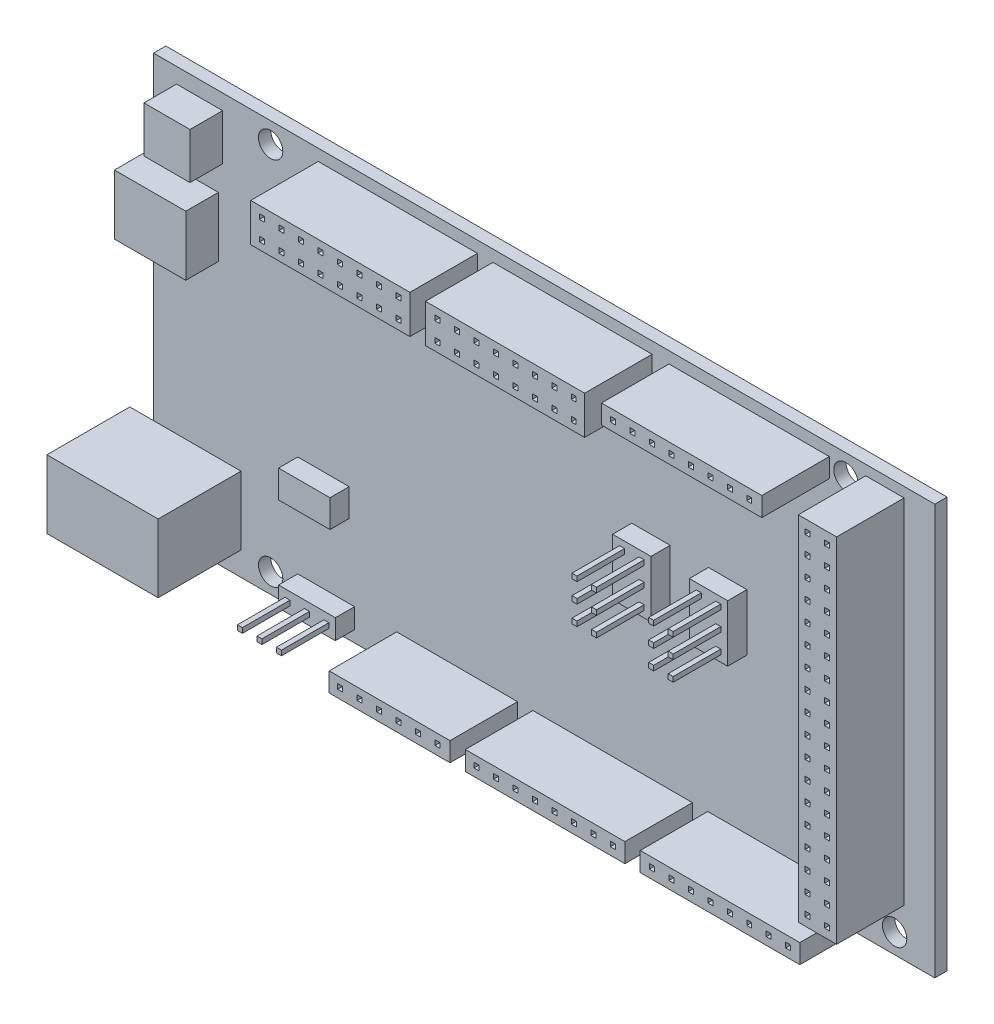
SolidWorks part; units mm, degrees
ref_plane "Front" through (0, 0, 0) normal (0, 0, 1) x (1, 0, 0)
ref_plane "Top" through (0, 0, 0) normal (0, 1, 0) x (1, 0, 0)
ref_plane "Right" through (0, 0, 0) normal (1, 0, 0) x (0, 0, -1)
sketch "sketchmap" plane through (0, 0, 0) normal (0, 0, 1) x (1, 0, 0)
  line L0 (-50.925, 26.75) -> (50.925, -26.75) construction
  line L1 (-50.925, 26.75) -> (50.925, 26.75)
  line L2 (-50.925, 26.75) -> (-50.925, -26.75)
  line L3 (-50.925, -26.75) -> (50.925, -26.75)
  line L4 (50.925, 26.75) -> (50.925, -26.75)
  dimension "D1" = 53.5
  dimension "D2" = 101.85
sketch "Sketch2" plane through (0, 0, 0) normal (0, 0, 1) x (1, 0, 0)
  line L0 (-35.6625, -24.1875) -> (45.6875, -24.1875) construction
  line L1 (-50.925, 26.75) -> (50.925, 26.75)
  line L2 (-50.925, 26.75) -> (-50.925, -26.75)
  line L3 (-50.925, -26.75) -> (50.925, -26.75)
  line L4 (50.925, 26.75) -> (50.925, -26.75)
  line L5 (-35.6625, 24.0625) -> (-35.6625, -24.1875) construction
  line L6 (39.3375, 24.0625) -> (-35.6625, 24.0625) construction
  line L10 (40.925, 24.0625) -> (50.925, 24.0625) construction
  line L11 (39.3375, 25.65) -> (39.3375, 26.75) construction
  circle A0 centre (45.6875, -24.1875) radius 1.5875
  circle A1 centre (-35.6625, -24.1875) radius 1.5875
  circle A2 centre (39.3375, 24.0625) radius 1.5875
  circle A3 centre (-35.6625, 24.0625) radius 1.5875
  dimension "D1" = 3.175
  dimension "D3" = 48.25
  dimension "D5" = 2.6875
  dimension "D4" = 5.2375
  dimension "D2" = 6.35
  dimension "D7" = 10
  dimension "D9" = 75
extrude "base board" add sketch "Sketch2" against normal blind 1.6
sketch "Sketch3" plane through (0, 0, 0) normal (0, 0, 1) x (1, 0, 0)
  line L1 (-29.457, 20.25) -> (-8.707, 20.25)
  line L2 (-29.457, 20.25) -> (-29.457, 25.25)
  line L3 (-29.457, 25.25) -> (-8.707, 25.25)
  line L4 (14.075, 20.25) -> (14.075, 25.25)
  line L5 (-50.925, 26.75) -> (50.925, 26.75) construction
  line L6 (50.925, 26.75) -> (50.925, -26.75) construction
  line L7 (16.275, 22.75) -> (37.175, 22.75)
  line L8 (16.275, 22.75) -> (16.275, 25.25)
  line L9 (16.275, 25.25) -> (37.175, 25.25)
  line L10 (37.175, 22.75) -> (37.175, 25.25)
  line L11 (41.925, 25.45) -> (46.925, 25.45)
  line L12 (41.925, 25.45) -> (41.925, -20.55)
  line L13 (41.925, -20.55) -> (46.925, -20.55)
  line L14 (46.925, 25.45) -> (46.925, -20.55)
  line L15 (-50.925, -26.75) -> (50.925, -26.75) construction
  line L16 (-8.707, 25.25) -> (-8.707, 20.25)
  line L17 (-6.675, 25.25) -> (-6.675, 20.25)
  line L18 (-6.675, 25.25) -> (14.075, 25.25)
  line L19 (-6.675, 20.25) -> (14.075, 20.25)
  line L20 (21.325, -25.25) -> (19.325, -25.25) construction
  line L21 (-19.225, -22.75) -> (-3.475, -22.75)
  line L22 (-19.225, -22.75) -> (-19.225, -25.25)
  line L23 (-19.225, -25.25) -> (-3.475, -25.25)
  line L24 (-3.475, -22.75) -> (-3.475, -25.25)
  line L25 (-1.475, -22.75) -> (19.325, -22.75)
  line L26 (-1.475, -22.75) -> (-1.475, -25.25)
  line L27 (-1.475, -25.25) -> (19.325, -25.25)
  line L28 (19.325, -22.75) -> (19.325, -25.25)
  line L29 (21.325, -22.75) -> (42.125, -22.75)
  line L30 (21.325, -22.75) -> (21.325, -25.25)
  line L31 (21.325, -25.25) -> (42.125, -25.25)
  line L32 (42.125, -22.75) -> (42.125, -25.25)
  line L33 (-3.475, -25.25) -> (-1.475, -25.25) construction
  line L34 (-1.475, -25.25) -> (-1.5179, -25.2056) construction
  line L35 (-50.925, 26.75) -> (-50.925, -26.75) construction
  line L36 (50.925, -26.75) -> (50.925, 26.75) construction
  dimension "D1" = 5
  dimension "D2" = 2.032
  dimension "D3" = 57.6
  dimension "D4" = 1.5
  dimension "D5" = 2.5
  dimension "D6" = 20.9
  dimension "D7" = 2.2
  dimension "D8" = 4
  dimension "D9" = 1.3
  dimension "D10" = 6.2
  dimension "D11" = 46
  dimension "D12" = 20.75
  dimension "D13" = 1.5
  dimension "D14" = 8.8
  dimension "D15" = 20.8
  dimension "D16" = 15.75
  dimension "D17" = 2
  dimension "D18" = 42.218
extrude "headers" add sketch "Sketch3" along normal blind 8.8
sketch "Sketch4" plane through (0, 0, 0) normal (0, 0, 1) x (1, 0, 0)
  line L0 (50.925, 26.75) -> (50.925, -26.75) construction
  line L1 (11.425, 4.85) -> (16.425, 4.85)
  line L2 (11.425, 4.85) -> (11.425, -2.55)
  line L3 (11.425, -2.55) -> (16.425, -2.55)
  line L4 (16.425, 4.85) -> (16.425, -2.55)
  line L5 (21.425, 4.85) -> (26.425, 4.85)
  line L6 (21.425, 4.85) -> (21.425, -2.55)
  line L7 (21.425, -2.55) -> (26.425, -2.55)
  line L8 (26.425, 4.85) -> (26.425, -2.55)
  line L9 (-50.925, 26.75) -> (50.925, 26.75) construction
  line L10 (-19.225, -22.75) -> (-19.225, -25.25) construction
  line L11 (-32.125, -22.65) -> (-24.725, -22.65)
  line L12 (-32.125, -22.65) -> (-32.125, -25.25)
  line L13 (-32.125, -25.25) -> (-24.725, -25.25)
  line L14 (-24.725, -22.65) -> (-24.725, -25.25)
  line L16 (-19.225, -25.25) -> (-3.475, -25.25) construction
  line L18 (-32.125, -9.45) -> (-25.425, -9.45)
  line L19 (-32.125, -9.45) -> (-32.125, -13.05)
  line L20 (-32.125, -13.05) -> (-25.425, -13.05)
  line L21 (-25.425, -9.45) -> (-25.425, -13.05)
  dimension "D1" = 5
  dimension "D2" = 7.4
  dimension "D3" = 29.5
  dimension "D4" = 5
  dimension "D5" = 29.3
  dimension "D6" = 2.6
  dimension "D7" = 7.4
  dimension "D8" = 5.5
  dimension "D9" = 6.7
  dimension "D10" = 3.6
  dimension "D11" = 9.6
extrude "pinbase" add sketch "Sketch4" along normal blind 2.5
sketch "Sketch5" plane through (0, 0, 0) normal (0, 0, 1) x (1, 0, 0)
  line L0 (-28.425, -22.65) -> (-28.425, -24.275) construction
  line L1 (-31.29, -23.625) -> (-30.64, -23.625)
  line L2 (-31.29, -23.625) -> (-31.29, -24.275)
  line L3 (-31.29, -24.275) -> (-30.64, -24.275)
  line L4 (-30.64, -23.625) -> (-30.64, -24.275)
  line L5 (-24.725, -22.65) -> (-32.125, -22.65) construction
  line L6 (-26.21, -23.625) -> (-26.21, -24.275)
  line L7 (-25.56, -24.275) -> (-26.21, -24.275)
  line L8 (-25.56, -23.625) -> (-25.56, -24.275)
  line L9 (-25.56, -23.625) -> (-26.21, -23.625)
  line L10 (-30.965, -24.275) -> (-30.965, -25.25) construction
  line L11 (-28.75, -24.275) -> (-28.1, -24.275)
  line L12 (-28.75, -24.275) -> (-28.75, -23.625)
  line L13 (-28.75, -23.625) -> (-28.1, -23.625)
  line L14 (-28.1, -24.275) -> (-28.1, -23.625)
  line L15 (-32.125, -25.25) -> (-24.725, -25.25) construction
  line L16 (-26.21, -23.625) -> (-25.56, -24.275) construction
  line L17 (-25.885, -22.65) -> (-25.885, -25.25) construction
  line L18 (-24.725, -22.65) -> (-32.125, -22.65) construction
  line L19 (13.925, 4.85) -> (13.925, -2.55) construction
  line L20 (12.33, 4.015) -> (12.98, 4.015)
  line L21 (12.33, 4.015) -> (12.33, 3.365)
  line L22 (12.33, 3.365) -> (12.98, 3.365)
  line L23 (12.98, 4.015) -> (12.98, 3.365)
  line L24 (16.425, 4.85) -> (11.425, 4.85) construction
  line L25 (11.425, -2.55) -> (16.425, -2.55) construction
  line L26 (15.52, 4.015) -> (15.52, 3.365)
  line L27 (15.52, 3.365) -> (14.87, 3.365)
  line L28 (14.87, 4.015) -> (14.87, 3.365)
  line L29 (15.52, 4.015) -> (14.87, 4.015)
  line L30 (12.33, 1.475) -> (12.98, 1.475)
  line L31 (12.33, 1.475) -> (12.33, 0.825)
  line L32 (12.33, 0.825) -> (12.98, 0.825)
  line L33 (12.98, 1.475) -> (12.98, 0.825)
  line L34 (15.52, 1.475) -> (15.52, 0.825)
  line L35 (15.52, 0.825) -> (14.87, 0.825)
  line L36 (14.87, 1.475) -> (14.87, 0.825)
  line L37 (15.52, 1.475) -> (14.87, 1.475)
  line L38 (12.33, -1.065) -> (12.98, -1.065)
  line L39 (12.33, -1.065) -> (12.33, -1.715)
  line L40 (12.33, -1.715) -> (12.98, -1.715)
  line L41 (12.98, -1.065) -> (12.98, -1.715)
  line L42 (15.52, -1.065) -> (15.52, -1.715)
  line L43 (15.52, -1.715) -> (14.87, -1.715)
  line L44 (14.87, -1.065) -> (14.87, -1.715)
  line L45 (15.52, -1.065) -> (14.87, -1.065)
  line L46 (13.925, 1.15) -> (12.98, 1.15) construction
  line L47 (16.425, 4.85) -> (21.425, 4.85) construction
  line L48 (18.925, 4.85) -> (18.925, 0) construction
  line L49 (22.33, -1.065) -> (22.98, -1.065)
  line L50 (22.98, -1.065) -> (22.98, -1.715)
  line L51 (22.33, -1.715) -> (22.98, -1.715)
  line L52 (22.33, -1.065) -> (22.33, -1.715)
  line L53 (22.33, 1.475) -> (22.98, 1.475)
  line L54 (22.98, 1.475) -> (22.98, 0.825)
  line L55 (22.33, 0.825) -> (22.98, 0.825)
  line L56 (22.33, 1.475) -> (22.33, 0.825)
  line L57 (22.33, 4.015) -> (22.98, 4.015)
  line L58 (22.98, 4.015) -> (22.98, 3.365)
  line L59 (22.33, 3.365) -> (22.98, 3.365)
  line L60 (22.33, 4.015) -> (22.33, 3.365)
  line L61 (24.87, -1.065) -> (24.87, -1.715)
  line L62 (25.52, -1.715) -> (24.87, -1.715)
  line L63 (25.52, -1.065) -> (25.52, -1.715)
  line L64 (25.52, -1.065) -> (24.87, -1.065)
  line L65 (24.87, 1.475) -> (24.87, 0.825)
  line L66 (25.52, 0.825) -> (24.87, 0.825)
  line L67 (25.52, 1.475) -> (25.52, 0.825)
  line L68 (25.52, 1.475) -> (24.87, 1.475)
  line L69 (24.87, 4.015) -> (24.87, 3.365)
  line L70 (25.52, 3.365) -> (24.87, 3.365)
  line L71 (25.52, 4.015) -> (25.52, 3.365)
  line L72 (25.52, 4.015) -> (24.87, 4.015)
  point P24 (-25.885, -23.95)
  dimension "D1" = 2.54
  dimension "D2" = 0.65
  dimension "D3" = 2.54
  dimension "D5" = 2.54
  dimension "D4" = 3
extrude "pins" add sketch "Sketch5" along normal blind 8.7 and the other way blind 3.2
sketch "Sketch6" plane through (0, 0, 0) normal (0, 0, 1) x (1, 0, 0)
  line L0 (-47.925, 18.75) -> (-41.925, 24.75) construction
  line L1 (-41.925, 24.75) -> (-47.925, 24.75)
  line L2 (-41.925, 24.75) -> (-41.925, 18.75)
  line L3 (-41.925, 18.75) -> (-47.925, 18.75)
  line L4 (-47.925, 24.75) -> (-47.925, 18.75)
  line L5 (-44.925, 21.75) -> (-47.925, 21.75) construction
  line L6 (-50.925, 26.75) -> (50.925, 26.75) construction
  line L7 (-47.925, 26.75) -> (-47.925, 24.75) construction
  line L8 (-50.925, 24.75) -> (-47.925, 24.75) construction
  line L9 (-50.925, 26.75) -> (-50.925, -26.75) construction
  line L11 (-42.475, 15.25) -> (-51.775, 15.25)
  line L12 (-42.475, 15.25) -> (-42.475, 7.45)
  line L13 (-42.475, 7.45) -> (-51.775, 7.45)
  line L14 (-51.775, 15.25) -> (-51.775, 7.45)
  dimension "D1" = 6
  dimension "D2" = 2
  dimension "D3" = 7.8
  dimension "D4" = 9.3
  dimension "D5" = 3
  dimension "D6" = 3.5
  dimension "D7" = 0.85
extrude "usbmini & button" add sketch "Sketch6" along normal blind 4.25
sketch "Sketch8" plane through (0, 0, 0) normal (0, 0, 1) x (1, 0, 0)
  line L0 (-50.925, 26.75) -> (-50.925, -26.75) construction
  line L1 (-39.525, -23.65) -> (-54.025, -23.65)
  line L2 (-39.525, -23.65) -> (-39.525, -14.75)
  line L3 (-39.525, -14.75) -> (-54.025, -14.75)
  line L4 (-54.025, -23.65) -> (-54.025, -14.75)
  line L5 (-50.925, -26.75) -> (50.925, -26.75) construction
  dimension "D1" = 8.9
  dimension "D2" = 14.5
  dimension "D3" = 3.1
  dimension "D4" = 3.1
extrude "power" add sketch "Sketch8" along normal blind 10.8
sketch "Sketch9" plane through (0, 0, -1.6) normal (0, 0, -1) x (-1, 0, 0)
  line L0 (50.925, 26.75) -> (50.925, -26.75) construction
  line L1 (42.175, -23.65) -> (45.175, -23.65)
  line L2 (42.175, -23.65) -> (42.175, -24.55)
  line L3 (42.175, -24.55) -> (45.175, -24.55)
  line L4 (45.175, -23.65) -> (45.175, -24.55)
  line L5 (50.925, -26.75) -> (-50.925, -26.75) construction
  line L6 (43.675, -23.65) -> (43.675, -17.3577) construction
  line L7 (39.975, -17.65) -> (40.875, -17.65)
  line L8 (39.975, -17.65) -> (39.975, -20.65)
  line L9 (39.975, -20.65) -> (40.875, -20.65)
  line L10 (40.875, -17.65) -> (40.875, -20.65)
  line L11 (46.475, -17.65) -> (46.475, -20.65)
  line L12 (47.375, -20.65) -> (46.475, -20.65)
  line L13 (47.375, -17.65) -> (47.375, -20.65)
  line L14 (47.375, -17.65) -> (46.475, -17.65)
  dimension "D1" = 3
  dimension "D2" = 0.9
  dimension "D3" = 5.75
  dimension "D4" = 2.2
  dimension "D5" = 5.6
  dimension "D6" = 3
extrude "underside solder tails" add sketch "Sketch9" along normal blind 1.8
sketch "Sketch10" plane through (0, 0, -1.6) normal (0, 0, -1) x (-1, 0, 0)
  line L0 (-41.925, 24) -> (-37.175, 24) construction
  line L2 (-37.175, 22.75) -> (-37.175, 25.25) construction
  line L3 (-41.925, 25.45) -> (-41.925, -20.55) construction
  line L4 (-41.925, 24) -> (-46.925, 24) construction
  line L5 (-46.925, -20.55) -> (-46.925, 25.45) construction
  line L6 (-44.425, 24) -> (-44.425, 25.45) construction
  line L7 (-46.925, 25.45) -> (-41.925, 25.45) construction
  line L8 (-46.02, 24.325) -> (-45.37, 23.675) construction
  line L9 (-46.02, 24.325) -> (-45.37, 24.325)
  line L10 (-46.02, 24.325) -> (-46.02, 23.675)
  line L11 (-46.02, 23.675) -> (-45.37, 23.675)
  line L12 (-45.37, 24.325) -> (-45.37, 23.675)
  line L13 (-45.695, 24) -> (-45.695, 24.325) construction
  line L14 (-24.87, 4.015) -> (-25.52, 4.015) construction
  point P17 (-45.695, 24)
  dimension "D1" = 2.54
extrude "underside rail tails" add sketch "Sketch10" along normal blind 1.6
pattern_linear "LPattern1" count 2 spacing 2.54 along (-1, 0, 0) count 18 spacing 2.54 along (0, -1, 0) of "underside rail tails"
sketch "Sketch11" plane through (0, 0, -1.6) normal (0, 0, -1) x (-1, 0, 0)
  line L0 (-45.37, 24.325) -> (-46.02, 24.325) construction
  line L1 (-35.86, 24.325) -> (-35.21, 24.325)
  line L2 (-35.86, 24.325) -> (-35.86, 23.675)
  line L3 (-35.86, 23.675) -> (-35.21, 23.675)
  line L4 (-35.21, 24.325) -> (-35.21, 23.675)
  line L5 (-42.83, 23.675) -> (-42.83, 24.325) construction
  line L6 (26.21, -24.275) -> (25.56, -24.275) construction
  line L7 (-40.94, -23.625) -> (-40.29, -23.625)
  line L8 (-40.94, -23.625) -> (-40.94, -24.275)
  line L9 (-40.94, -24.275) -> (-40.29, -24.275)
  line L10 (-40.29, -23.625) -> (-40.29, -24.275)
  line L11 (-42.83, -19.505) -> (-42.83, -18.855) construction
  dimension "D1" = 7.62
  dimension "D2" = 2.54
extrude "Boss-Extrude9" add sketch "Sketch11" along normal up to surface (1.6 mm away) up to face at (45.695, 24, -3.2)
pattern_linear "LPattern2" count 8 spacing 2.54 along (-1, 0, 0) of "Boss-Extrude9"
sketch "Sketch12" plane through (0, 0, -1.6) normal (0, 0, -1) x (-1, 0, 0)
  line L0 (-18.08, -23.625) -> (-17.43, -24.275) construction
  line L1 (-18.08, -23.625) -> (-17.43, -23.625)
  line L2 (-18.08, -23.625) -> (-18.08, -24.275)
  line L3 (-18.08, -24.275) -> (-17.43, -24.275)
  line L4 (-17.43, -23.625) -> (-17.43, -24.275)
  line L5 (-22.51, -23.625) -> (-23.16, -23.625) construction
  line L6 (-18.08, 24.325) -> (-18.08, 23.675) construction
extrude "Boss-Extrude10" add sketch "Sketch12" along normal up to surface (1.6 mm away) up to face at (22.835, -23.95, -3.2)
pattern_linear "LPattern3" count 15 spacing 2.54 along (-1, 0, 0) skipping (8, 0) of "Boss-Extrude10"
sketch "Sketch13" plane through (0, 0, -1.6) normal (0, 0, -1) x (-1, 0, 0)
  line L0 (-17.43, 24.325) -> (-18.08, 24.325) construction
  line L1 (-12.98, 24.325) -> (-12.33, 24.325)
  line L2 (-12.98, 24.325) -> (-12.98, 23.675)
  line L3 (-12.98, 23.675) -> (-12.33, 23.675)
  line L4 (-12.33, 24.325) -> (-12.33, 23.675)
  line L5 (-12.98, 3.365) -> (-12.98, 4.015) construction
extrude "Boss-Extrude11" add sketch "Sketch13" along normal up to surface (1.6 mm away) up to face at (45.695, 24, -3.2)
pattern_linear "LPattern4" count 17 spacing 2.54 along (-1, 0, 0) count 2 spacing 2.54 along (0, -1, 0) skipping (8, 0), (8, 1) of "Boss-Extrude11"
sketch "Sketch14" plane through (0, 0, 10.8) normal (0, 0, 1) x (1, 0, 0)
  line L0 (-20, 18.5) -> (40, -21.5) construction
  line L1 (-20, 18.5) -> (40, 18.5)
  line L2 (-20, 18.5) -> (-20, -21.5)
  line L3 (-20, -21.5) -> (40, -21.5)
  line L4 (40, 18.5) -> (40, -21.5)
  line L5 (10, -1.5) -> (40, -1.5) construction
  line L6 (10, -1.5) -> (10, 18.5) construction
  line L7 (10, -1.5) -> (-15, -1.5) construction
  line L8 (-16.75, -18.5) -> (36.75, 15.5) construction
  line L9 (-16.75, 15.5) -> (36.75, 15.5) construction
  line L10 (-16.75, 15.5) -> (-16.75, -18.5) construction
  line L11 (-16.75, -18.5) -> (36.75, -18.5) construction
  line L12 (36.75, 15.5) -> (36.75, -18.5) construction
  circle A0 centre (-16.75, 15.5) radius 1.65
  circle A1 centre (-16.75, -18.5) radius 1.65
  circle A2 centre (36.75, -18.5) radius 1.65
  circle A3 centre (36.75, 15.5) radius 1.65
  dimension "D8" = 3.3
  dimension "D1" = 60
  dimension "D2" = 40
  dimension "D3" = 25
  dimension "D4" = 1.5
  dimension "D5" = 10
  dimension "D6" = 34
  dimension "D7" = 53.5
sketch "Sketch15" plane through (0, 0, 8.8) normal (0, 0, 1) x (1, 0, 0)
  line L0 (46.02, 24.325) -> (46.02, 23.675) construction
  line L1 (46.02, 23.675) -> (45.37, 23.675) construction
  line L2 (45.37, 23.675) -> (45.37, 24.325) construction
  line L3 (45.37, 24.325) -> (46.02, 24.325) construction
  line L4 (46.02, 21.785) -> (46.02, 21.135) construction
  line L5 (46.02, 21.135) -> (45.37, 21.135) construction
  line L6 (45.37, 21.135) -> (45.37, 21.785) construction
  line L7 (45.37, 21.785) -> (46.02, 21.785) construction
  line L8 (46.02, 19.245) -> (46.02, 18.595) construction
  line L9 (46.02, 18.595) -> (45.37, 18.595) construction
  line L10 (45.37, 18.595) -> (45.37, 19.245) construction
  line L11 (45.37, 19.245) -> (46.02, 19.245) construction
  line L12 (46.02, 16.705) -> (46.02, 16.055) construction
  line L13 (46.02, 16.055) -> (45.37, 16.055) construction
  line L14 (45.37, 16.055) -> (45.37, 16.705) construction
  line L15 (45.37, 16.705) -> (46.02, 16.705) construction
  line L16 (46.02, 14.165) -> (46.02, 13.515) construction
  line L17 (46.02, 13.515) -> (45.37, 13.515) construction
  line L18 (45.37, 13.515) -> (45.37, 14.165) construction
  line L19 (45.37, 14.165) -> (46.02, 14.165) construction
  line L20 (46.02, 11.625) -> (46.02, 10.975) construction
  line L21 (46.02, 10.975) -> (45.37, 10.975) construction
  line L22 (45.37, 10.975) -> (45.37, 11.625) construction
  line L23 (45.37, 11.625) -> (46.02, 11.625) construction
  line L24 (46.02, 9.085) -> (46.02, 8.435) construction
  line L25 (46.02, 8.435) -> (45.37, 8.435) construction
  line L26 (45.37, 8.435) -> (45.37, 9.085) construction
  line L27 (45.37, 9.085) -> (46.02, 9.085) construction
  line L28 (46.02, 6.545) -> (46.02, 5.895) construction
  line L29 (46.02, 5.895) -> (45.37, 5.895) construction
  line L30 (45.37, 5.895) -> (45.37, 6.545) construction
  line L31 (45.37, 6.545) -> (46.02, 6.545) construction
  line L32 (46.02, 4.005) -> (46.02, 3.355) construction
  line L33 (46.02, 3.355) -> (45.37, 3.355) construction
  line L34 (45.37, 3.355) -> (45.37, 4.005) construction
  line L35 (45.37, 4.005) -> (46.02, 4.005) construction
  line L36 (46.02, 1.465) -> (46.02, 0.815) construction
  line L37 (46.02, 0.815) -> (45.37, 0.815) construction
  line L38 (45.37, 0.815) -> (45.37, 1.465) construction
  line L39 (45.37, 1.465) -> (46.02, 1.465) construction
  line L40 (46.02, -1.075) -> (46.02, -1.725) construction
  line L41 (46.02, -1.725) -> (45.37, -1.725) construction
  line L42 (45.37, -1.725) -> (45.37, -1.075) construction
  line L43 (45.37, -1.075) -> (46.02, -1.075) construction
  line L44 (46.02, -3.615) -> (46.02, -4.265) construction
  line L45 (46.02, -4.265) -> (45.37, -4.265) construction
  line L46 (45.37, -4.265) -> (45.37, -3.615) construction
  line L47 (45.37, -3.615) -> (46.02, -3.615) construction
  line L48 (46.02, -6.155) -> (46.02, -6.805) construction
  line L49 (46.02, -6.805) -> (45.37, -6.805) construction
  line L50 (45.37, -6.805) -> (45.37, -6.155) construction
  line L51 (45.37, -6.155) -> (46.02, -6.155) construction
  line L52 (46.02, -8.695) -> (46.02, -9.345) construction
  line L53 (46.02, -9.345) -> (45.37, -9.345) construction
  line L54 (45.37, -9.345) -> (45.37, -8.695) construction
  line L55 (45.37, -8.695) -> (46.02, -8.695) construction
  line L56 (46.02, -11.235) -> (46.02, -11.885) construction
  line L57 (46.02, -11.885) -> (45.37, -11.885) construction
  line L58 (45.37, -11.885) -> (45.37, -11.235) construction
  line L59 (45.37, -11.235) -> (46.02, -11.235) construction
  line L60 (46.02, -13.775) -> (46.02, -14.425) construction
  line L61 (46.02, -14.425) -> (45.37, -14.425) construction
  line L62 (45.37, -14.425) -> (45.37, -13.775) construction
  line L63 (45.37, -13.775) -> (46.02, -13.775) construction
  line L64 (46.02, -16.315) -> (46.02, -16.965) construction
  line L65 (46.02, -16.965) -> (45.37, -16.965) construction
  line L66 (45.37, -16.965) -> (45.37, -16.315) construction
  line L67 (45.37, -16.315) -> (46.02, -16.315) construction
  line L68 (46.02, -18.855) -> (46.02, -19.505) construction
  line L69 (46.02, -19.505) -> (45.37, -19.505) construction
  line L70 (45.37, -19.505) -> (45.37, -18.855) construction
  line L71 (45.37, -18.855) -> (46.02, -18.855) construction
  line L72 (46.02, 24.325) -> (46.02, 23.675)
  line L73 (46.02, 23.675) -> (45.37, 23.675)
  line L74 (45.37, 23.675) -> (45.37, 24.325)
  line L75 (45.37, 24.325) -> (46.02, 24.325)
  line L76 (46.02, 21.785) -> (46.02, 21.135)
  line L77 (46.02, 21.135) -> (45.37, 21.135)
  line L78 (45.37, 21.135) -> (45.37, 21.785)
  line L79 (45.37, 21.785) -> (46.02, 21.785)
  line L80 (46.02, 19.245) -> (46.02, 18.595)
  line L81 (46.02, 18.595) -> (45.37, 18.595)
  line L82 (45.37, 18.595) -> (45.37, 19.245)
  line L83 (45.37, 19.245) -> (46.02, 19.245)
  line L84 (46.02, 16.705) -> (46.02, 16.055)
  line L85 (46.02, 16.055) -> (45.37, 16.055)
  line L86 (45.37, 16.055) -> (45.37, 16.705)
  line L87 (45.37, 16.705) -> (46.02, 16.705)
  line L88 (46.02, 14.165) -> (46.02, 13.515)
  line L89 (46.02, 13.515) -> (45.37, 13.515)
  line L90 (45.37, 13.515) -> (45.37, 14.165)
  line L91 (45.37, 14.165) -> (46.02, 14.165)
  line L92 (46.02, 11.625) -> (46.02, 10.975)
  line L93 (46.02, 10.975) -> (45.37, 10.975)
  line L94 (45.37, 10.975) -> (45.37, 11.625)
  line L95 (45.37, 11.625) -> (46.02, 11.625)
  line L96 (46.02, 9.085) -> (46.02, 8.435)
  line L97 (46.02, 8.435) -> (45.37, 8.435)
  line L98 (45.37, 8.435) -> (45.37, 9.085)
  line L99 (45.37, 9.085) -> (46.02, 9.085)
  line L100 (46.02, 6.545) -> (46.02, 5.895)
  line L101 (46.02, 5.895) -> (45.37, 5.895)
  line L102 (45.37, 5.895) -> (45.37, 6.545)
  line L103 (45.37, 6.545) -> (46.02, 6.545)
  line L104 (46.02, 4.005) -> (46.02, 3.355)
  line L105 (46.02, 3.355) -> (45.37, 3.355)
  line L106 (45.37, 3.355) -> (45.37, 4.005)
  line L107 (45.37, 4.005) -> (46.02, 4.005)
  line L108 (46.02, 1.465) -> (46.02, 0.815)
  line L109 (46.02, 0.815) -> (45.37, 0.815)
  line L110 (45.37, 0.815) -> (45.37, 1.465)
  line L111 (45.37, 1.465) -> (46.02, 1.465)
  line L112 (46.02, -1.075) -> (46.02, -1.725)
  line L113 (46.02, -1.725) -> (45.37, -1.725)
  line L114 (45.37, -1.725) -> (45.37, -1.075)
  line L115 (45.37, -1.075) -> (46.02, -1.075)
  line L116 (46.02, -3.615) -> (46.02, -4.265)
  line L117 (46.02, -4.265) -> (45.37, -4.265)
  line L118 (45.37, -4.265) -> (45.37, -3.615)
  line L119 (45.37, -3.615) -> (46.02, -3.615)
  line L120 (46.02, -6.155) -> (46.02, -6.805)
  line L121 (46.02, -6.805) -> (45.37, -6.805)
  line L122 (45.37, -6.805) -> (45.37, -6.155)
  line L123 (45.37, -6.155) -> (46.02, -6.155)
  line L124 (46.02, -8.695) -> (46.02, -9.345)
  line L125 (46.02, -9.345) -> (45.37, -9.345)
  line L126 (45.37, -9.345) -> (45.37, -8.695)
  line L127 (45.37, -8.695) -> (46.02, -8.695)
  line L128 (46.02, -11.235) -> (46.02, -11.885)
  line L129 (46.02, -11.885) -> (45.37, -11.885)
  line L130 (45.37, -11.885) -> (45.37, -11.235)
  line L131 (45.37, -11.235) -> (46.02, -11.235)
  line L132 (46.02, -13.775) -> (46.02, -14.425)
  line L133 (46.02, -14.425) -> (45.37, -14.425)
  line L134 (45.37, -14.425) -> (45.37, -13.775)
  line L135 (45.37, -13.775) -> (46.02, -13.775)
  line L136 (46.02, -16.315) -> (46.02, -16.965)
  line L137 (46.02, -16.965) -> (45.37, -16.965)
  line L138 (45.37, -16.965) -> (45.37, -16.315)
  line L139 (45.37, -16.315) -> (46.02, -16.315)
  line L140 (46.02, -18.855) -> (46.02, -19.505)
  line L141 (46.02, -19.505) -> (45.37, -19.505)
  line L142 (45.37, -19.505) -> (45.37, -18.855)
  line L143 (45.37, -18.855) -> (46.02, -18.855)
  line L144 (43.48, 24.325) -> (43.48, 23.675) construction
  line L145 (43.48, 23.675) -> (42.83, 23.675) construction
  line L146 (42.83, 23.675) -> (42.83, 24.325) construction
  line L147 (42.83, 24.325) -> (43.48, 24.325) construction
  line L148 (43.48, 21.785) -> (43.48, 21.135) construction
  line L149 (43.48, 21.135) -> (42.83, 21.135) construction
  line L150 (42.83, 21.135) -> (42.83, 21.785) construction
  line L151 (42.83, 21.785) -> (43.48, 21.785) construction
  line L152 (43.48, 19.245) -> (43.48, 18.595) construction
  line L153 (43.48, 18.595) -> (42.83, 18.595) construction
  line L154 (42.83, 18.595) -> (42.83, 19.245) construction
  line L155 (42.83, 19.245) -> (43.48, 19.245) construction
  line L156 (43.48, 16.705) -> (43.48, 16.055) construction
  line L157 (43.48, 16.055) -> (42.83, 16.055) construction
  line L158 (42.83, 16.055) -> (42.83, 16.705) construction
  line L159 (42.83, 16.705) -> (43.48, 16.705) construction
  line L160 (43.48, 14.165) -> (43.48, 13.515) construction
  line L161 (43.48, 13.515) -> (42.83, 13.515) construction
  line L162 (42.83, 13.515) -> (42.83, 14.165) construction
  line L163 (42.83, 14.165) -> (43.48, 14.165) construction
  line L164 (43.48, 11.625) -> (43.48, 10.975) construction
  line L165 (43.48, 10.975) -> (42.83, 10.975) construction
  line L166 (42.83, 10.975) -> (42.83, 11.625) construction
  line L167 (42.83, 11.625) -> (43.48, 11.625) construction
  line L168 (43.48, 9.085) -> (43.48, 8.435) construction
  line L169 (43.48, 8.435) -> (42.83, 8.435) construction
  line L170 (42.83, 8.435) -> (42.83, 9.085) construction
  line L171 (42.83, 9.085) -> (43.48, 9.085) construction
  line L172 (43.48, 6.545) -> (43.48, 5.895) construction
  line L173 (43.48, 5.895) -> (42.83, 5.895) construction
  line L174 (42.83, 5.895) -> (42.83, 6.545) construction
  line L175 (42.83, 6.545) -> (43.48, 6.545) construction
  line L176 (43.48, 4.005) -> (43.48, 3.355) construction
  line L177 (43.48, 3.355) -> (42.83, 3.355) construction
  line L178 (42.83, 3.355) -> (42.83, 4.005) construction
  line L179 (42.83, 4.005) -> (43.48, 4.005) construction
  line L180 (43.48, 1.465) -> (43.48, 0.815) construction
  line L181 (43.48, 0.815) -> (42.83, 0.815) construction
  line L182 (42.83, 0.815) -> (42.83, 1.465) construction
  line L183 (42.83, 1.465) -> (43.48, 1.465) construction
  line L184 (43.48, -1.075) -> (43.48, -1.725) construction
  line L185 (43.48, -1.725) -> (42.83, -1.725) construction
  line L186 (42.83, -1.725) -> (42.83, -1.075) construction
  line L187 (42.83, -1.075) -> (43.48, -1.075) construction
  line L188 (43.48, -3.615) -> (43.48, -4.265) construction
  line L189 (43.48, -4.265) -> (42.83, -4.265) construction
  line L190 (42.83, -4.265) -> (42.83, -3.615) construction
  line L191 (42.83, -3.615) -> (43.48, -3.615) construction
  line L192 (43.48, -6.155) -> (43.48, -6.805) construction
  line L193 (43.48, -6.805) -> (42.83, -6.805) construction
  line L194 (42.83, -6.805) -> (42.83, -6.155) construction
  line L195 (42.83, -6.155) -> (43.48, -6.155) construction
  line L196 (43.48, -8.695) -> (43.48, -9.345) construction
  line L197 (43.48, -9.345) -> (42.83, -9.345) construction
  line L198 (42.83, -9.345) -> (42.83, -8.695) construction
  line L199 (42.83, -8.695) -> (43.48, -8.695) construction
  line L200 (43.48, -11.235) -> (43.48, -11.885) construction
  line L201 (43.48, -11.885) -> (42.83, -11.885) construction
  line L202 (42.83, -11.885) -> (42.83, -11.235) construction
  line L203 (42.83, -11.235) -> (43.48, -11.235) construction
  line L204 (43.48, -13.775) -> (43.48, -14.425) construction
  line L205 (43.48, -14.425) -> (42.83, -14.425) construction
  line L206 (42.83, -14.425) -> (42.83, -13.775) construction
  line L207 (42.83, -13.775) -> (43.48, -13.775) construction
  line L208 (43.48, -16.315) -> (43.48, -16.965) construction
  line L209 (43.48, -16.965) -> (42.83, -16.965) construction
  line L210 (42.83, -16.965) -> (42.83, -16.315) construction
  line L211 (42.83, -16.315) -> (43.48, -16.315) construction
  line L212 (43.48, -18.855) -> (43.48, -19.505) construction
  line L213 (43.48, -19.505) -> (42.83, -19.505) construction
  line L214 (42.83, -19.505) -> (42.83, -18.855) construction
  line L215 (42.83, -18.855) -> (43.48, -18.855) construction
  line L216 (43.48, 24.325) -> (43.48, 23.675)
  line L217 (43.48, 23.675) -> (42.83, 23.675)
  line L218 (42.83, 23.675) -> (42.83, 24.325)
  line L219 (42.83, 24.325) -> (43.48, 24.325)
  line L220 (43.48, 21.785) -> (43.48, 21.135)
  line L221 (43.48, 21.135) -> (42.83, 21.135)
  line L222 (42.83, 21.135) -> (42.83, 21.785)
  line L223 (42.83, 21.785) -> (43.48, 21.785)
  line L224 (43.48, 19.245) -> (43.48, 18.595)
  line L225 (43.48, 18.595) -> (42.83, 18.595)
  line L226 (42.83, 18.595) -> (42.83, 19.245)
  line L227 (42.83, 19.245) -> (43.48, 19.245)
  line L228 (43.48, 16.705) -> (43.48, 16.055)
  line L229 (43.48, 16.055) -> (42.83, 16.055)
  line L230 (42.83, 16.055) -> (42.83, 16.705)
  line L231 (42.83, 16.705) -> (43.48, 16.705)
  line L232 (43.48, 14.165) -> (43.48, 13.515)
  line L233 (43.48, 13.515) -> (42.83, 13.515)
  line L234 (42.83, 13.515) -> (42.83, 14.165)
  line L235 (42.83, 14.165) -> (43.48, 14.165)
  line L236 (43.48, 11.625) -> (43.48, 10.975)
  line L237 (43.48, 10.975) -> (42.83, 10.975)
  line L238 (42.83, 10.975) -> (42.83, 11.625)
  line L239 (42.83, 11.625) -> (43.48, 11.625)
  line L240 (43.48, 9.085) -> (43.48, 8.435)
  line L241 (43.48, 8.435) -> (42.83, 8.435)
  line L242 (42.83, 8.435) -> (42.83, 9.085)
  line L243 (42.83, 9.085) -> (43.48, 9.085)
  line L244 (43.48, 6.545) -> (43.48, 5.895)
  line L245 (43.48, 5.895) -> (42.83, 5.895)
  line L246 (42.83, 5.895) -> (42.83, 6.545)
  line L247 (42.83, 6.545) -> (43.48, 6.545)
  line L248 (43.48, 4.005) -> (43.48, 3.355)
  line L249 (43.48, 3.355) -> (42.83, 3.355)
  line L250 (42.83, 3.355) -> (42.83, 4.005)
  line L251 (42.83, 4.005) -> (43.48, 4.005)
  line L252 (43.48, 1.465) -> (43.48, 0.815)
  line L253 (43.48, 0.815) -> (42.83, 0.815)
  line L254 (42.83, 0.815) -> (42.83, 1.465)
  line L255 (42.83, 1.465) -> (43.48, 1.465)
  line L256 (43.48, -1.075) -> (43.48, -1.725)
  line L257 (43.48, -1.725) -> (42.83, -1.725)
  line L258 (42.83, -1.725) -> (42.83, -1.075)
  line L259 (42.83, -1.075) -> (43.48, -1.075)
  line L260 (43.48, -3.615) -> (43.48, -4.265)
  line L261 (43.48, -4.265) -> (42.83, -4.265)
  line L262 (42.83, -4.265) -> (42.83, -3.615)
  line L263 (42.83, -3.615) -> (43.48, -3.615)
  line L264 (43.48, -6.155) -> (43.48, -6.805)
  line L265 (43.48, -6.805) -> (42.83, -6.805)
  line L266 (42.83, -6.805) -> (42.83, -6.155)
  line L267 (42.83, -6.155) -> (43.48, -6.155)
  line L268 (43.48, -8.695) -> (43.48, -9.345)
  line L269 (43.48, -9.345) -> (42.83, -9.345)
  line L270 (42.83, -9.345) -> (42.83, -8.695)
  line L271 (42.83, -8.695) -> (43.48, -8.695)
  line L272 (43.48, -11.235) -> (43.48, -11.885)
  line L273 (43.48, -11.885) -> (42.83, -11.885)
  line L274 (42.83, -11.885) -> (42.83, -11.235)
  line L275 (42.83, -11.235) -> (43.48, -11.235)
  line L276 (43.48, -13.775) -> (43.48, -14.425)
  line L277 (43.48, -14.425) -> (42.83, -14.425)
  line L278 (42.83, -14.425) -> (42.83, -13.775)
  line L279 (42.83, -13.775) -> (43.48, -13.775)
  line L280 (43.48, -16.315) -> (43.48, -16.965)
  line L281 (43.48, -16.965) -> (42.83, -16.965)
  line L282 (42.83, -16.965) -> (42.83, -16.315)
  line L283 (42.83, -16.315) -> (43.48, -16.315)
  line L284 (43.48, -18.855) -> (43.48, -19.505)
  line L285 (43.48, -19.505) -> (42.83, -19.505)
  line L286 (42.83, -19.505) -> (42.83, -18.855)
  line L287 (42.83, -18.855) -> (43.48, -18.855)
  line L288 (35.21, 24.325) -> (35.86, 24.325) construction
  line L289 (35.86, 24.325) -> (35.86, 23.675) construction
  line L290 (35.86, 23.675) -> (35.21, 23.675) construction
  line L291 (35.21, 23.675) -> (35.21, 24.325) construction
  line L292 (32.67, 24.325) -> (33.32, 24.325) construction
  line L293 (33.32, 24.325) -> (33.32, 23.675) construction
  line L294 (33.32, 23.675) -> (32.67, 23.675) construction
  line L295 (32.67, 23.675) -> (32.67, 24.325) construction
  line L296 (30.13, 24.325) -> (30.78, 24.325) construction
  line L297 (30.78, 24.325) -> (30.78, 23.675) construction
  line L298 (30.78, 23.675) -> (30.13, 23.675) construction
  line L299 (30.13, 23.675) -> (30.13, 24.325) construction
  line L300 (27.59, 24.325) -> (28.24, 24.325) construction
  line L301 (28.24, 24.325) -> (28.24, 23.675) construction
  line L302 (28.24, 23.675) -> (27.59, 23.675) construction
  line L303 (27.59, 23.675) -> (27.59, 24.325) construction
  line L304 (25.05, 24.325) -> (25.7, 24.325) construction
  line L305 (25.7, 24.325) -> (25.7, 23.675) construction
  line L306 (25.7, 23.675) -> (25.05, 23.675) construction
  line L307 (25.05, 23.675) -> (25.05, 24.325) construction
  line L308 (22.51, 24.325) -> (23.16, 24.325) construction
  line L309 (23.16, 24.325) -> (23.16, 23.675) construction
  line L310 (23.16, 23.675) -> (22.51, 23.675) construction
  line L311 (22.51, 23.675) -> (22.51, 24.325) construction
  line L312 (19.97, 24.325) -> (20.62, 24.325) construction
  line L313 (20.62, 24.325) -> (20.62, 23.675) construction
  line L314 (20.62, 23.675) -> (19.97, 23.675) construction
  line L315 (19.97, 23.675) -> (19.97, 24.325) construction
  line L316 (17.43, 24.325) -> (18.08, 24.325) construction
  line L317 (18.08, 24.325) -> (18.08, 23.675) construction
  line L318 (18.08, 23.675) -> (17.43, 23.675) construction
  line L319 (17.43, 23.675) -> (17.43, 24.325) construction
  line L320 (12.33, 24.325) -> (12.98, 24.325) construction
  line L321 (12.98, 24.325) -> (12.98, 23.675) construction
  line L322 (12.98, 23.675) -> (12.33, 23.675) construction
  line L323 (12.33, 23.675) -> (12.33, 24.325) construction
  line L324 (12.33, 21.785) -> (12.98, 21.785) construction
  line L325 (12.98, 21.785) -> (12.98, 21.135) construction
  line L326 (12.98, 21.135) -> (12.33, 21.135) construction
  line L327 (12.33, 21.135) -> (12.33, 21.785) construction
  line L328 (9.79, 24.325) -> (10.44, 24.325) construction
  line L329 (10.44, 24.325) -> (10.44, 23.675) construction
  line L330 (10.44, 23.675) -> (9.79, 23.675) construction
  line L331 (9.79, 23.675) -> (9.79, 24.325) construction
  line L332 (9.79, 21.785) -> (10.44, 21.785) construction
  line L333 (10.44, 21.785) -> (10.44, 21.135) construction
  line L334 (10.44, 21.135) -> (9.79, 21.135) construction
  line L335 (9.79, 21.135) -> (9.79, 21.785) construction
  line L336 (7.25, 24.325) -> (7.9, 24.325) construction
  line L337 (7.9, 24.325) -> (7.9, 23.675) construction
  line L338 (7.9, 23.675) -> (7.25, 23.675) construction
  line L339 (7.25, 23.675) -> (7.25, 24.325) construction
  line L340 (7.25, 21.785) -> (7.9, 21.785) construction
  line L341 (7.9, 21.785) -> (7.9, 21.135) construction
  line L342 (7.9, 21.135) -> (7.25, 21.135) construction
  line L343 (7.25, 21.135) -> (7.25, 21.785) construction
  line L344 (4.71, 24.325) -> (5.36, 24.325) construction
  line L345 (5.36, 24.325) -> (5.36, 23.675) construction
  line L346 (5.36, 23.675) -> (4.71, 23.675) construction
  line L347 (4.71, 23.675) -> (4.71, 24.325) construction
  line L348 (4.71, 21.785) -> (5.36, 21.785) construction
  line L349 (5.36, 21.785) -> (5.36, 21.135) construction
  line L350 (5.36, 21.135) -> (4.71, 21.135) construction
  line L351 (4.71, 21.135) -> (4.71, 21.785) construction
  line L352 (2.17, 24.325) -> (2.82, 24.325) construction
  line L353 (2.82, 24.325) -> (2.82, 23.675) construction
  line L354 (2.82, 23.675) -> (2.17, 23.675) construction
  line L355 (2.17, 23.675) -> (2.17, 24.325) construction
  line L356 (2.17, 21.785) -> (2.82, 21.785) construction
  line L357 (2.82, 21.785) -> (2.82, 21.135) construction
  line L358 (2.82, 21.135) -> (2.17, 21.135) construction
  line L359 (2.17, 21.135) -> (2.17, 21.785) construction
  line L360 (-0.37, 24.325) -> (0.28, 24.325) construction
  line L361 (0.28, 24.325) -> (0.28, 23.675) construction
  line L362 (0.28, 23.675) -> (-0.37, 23.675) construction
  line L363 (-0.37, 23.675) -> (-0.37, 24.325) construction
  line L364 (-0.37, 21.785) -> (0.28, 21.785) construction
  line L365 (0.28, 21.785) -> (0.28, 21.135) construction
  line L366 (0.28, 21.135) -> (-0.37, 21.135) construction
  line L367 (-0.37, 21.135) -> (-0.37, 21.785) construction
  line L368 (-2.91, 24.325) -> (-2.26, 24.325) construction
  line L369 (-2.26, 24.325) -> (-2.26, 23.675) construction
  line L370 (-2.26, 23.675) -> (-2.91, 23.675) construction
  line L371 (-2.91, 23.675) -> (-2.91, 24.325) construction
  line L372 (-2.91, 21.785) -> (-2.26, 21.785) construction
  line L373 (-2.26, 21.785) -> (-2.26, 21.135) construction
  line L374 (-2.26, 21.135) -> (-2.91, 21.135) construction
  line L375 (-2.91, 21.135) -> (-2.91, 21.785) construction
  line L376 (-5.45, 24.325) -> (-4.8, 24.325) construction
  line L377 (-4.8, 24.325) -> (-4.8, 23.675) construction
  line L378 (-4.8, 23.675) -> (-5.45, 23.675) construction
  line L379 (-5.45, 23.675) -> (-5.45, 24.325) construction
  line L380 (-5.45, 21.785) -> (-4.8, 21.785) construction
  line L381 (-4.8, 21.785) -> (-4.8, 21.135) construction
  line L382 (-4.8, 21.135) -> (-5.45, 21.135) construction
  line L383 (-5.45, 21.135) -> (-5.45, 21.785) construction
  line L384 (-10.53, 24.325) -> (-9.88, 24.325) construction
  line L385 (-9.88, 24.325) -> (-9.88, 23.675) construction
  line L386 (-9.88, 23.675) -> (-10.53, 23.675) construction
  line L387 (-10.53, 23.675) -> (-10.53, 24.325) construction
  line L388 (-10.53, 21.785) -> (-9.88, 21.785) construction
  line L389 (-9.88, 21.785) -> (-9.88, 21.135) construction
  line L390 (-9.88, 21.135) -> (-10.53, 21.135) construction
  line L391 (-10.53, 21.135) -> (-10.53, 21.785) construction
  line L392 (-13.07, 24.325) -> (-12.42, 24.325) construction
  line L393 (-12.42, 24.325) -> (-12.42, 23.675) construction
  line L394 (-12.42, 23.675) -> (-13.07, 23.675) construction
  line L395 (-13.07, 23.675) -> (-13.07, 24.325) construction
  line L396 (-13.07, 21.785) -> (-12.42, 21.785) construction
  line L397 (-12.42, 21.785) -> (-12.42, 21.135) construction
  line L398 (-12.42, 21.135) -> (-13.07, 21.135) construction
  line L399 (-13.07, 21.135) -> (-13.07, 21.785) construction
  line L400 (-15.61, 24.325) -> (-14.96, 24.325) construction
  line L401 (-14.96, 24.325) -> (-14.96, 23.675) construction
  line L402 (-14.96, 23.675) -> (-15.61, 23.675) construction
  line L403 (-15.61, 23.675) -> (-15.61, 24.325) construction
  line L404 (-15.61, 21.785) -> (-14.96, 21.785) construction
  line L405 (-14.96, 21.785) -> (-14.96, 21.135) construction
  line L406 (-14.96, 21.135) -> (-15.61, 21.135) construction
  line L407 (-15.61, 21.135) -> (-15.61, 21.785) construction
  line L408 (-18.15, 24.325) -> (-17.5, 24.325) construction
  line L409 (-17.5, 24.325) -> (-17.5, 23.675) construction
  line L410 (-17.5, 23.675) -> (-18.15, 23.675) construction
  line L411 (-18.15, 23.675) -> (-18.15, 24.325) construction
  line L412 (-18.15, 21.785) -> (-17.5, 21.785) construction
  line L413 (-17.5, 21.785) -> (-17.5, 21.135) construction
  line L414 (-17.5, 21.135) -> (-18.15, 21.135) construction
  line L415 (-18.15, 21.135) -> (-18.15, 21.785) construction
  line L416 (-20.69, 24.325) -> (-20.04, 24.325) construction
  line L417 (-20.04, 24.325) -> (-20.04, 23.675) construction
  line L418 (-20.04, 23.675) -> (-20.69, 23.675) construction
  line L419 (-20.69, 23.675) -> (-20.69, 24.325) construction
  line L420 (-20.69, 21.785) -> (-20.04, 21.785) construction
  line L421 (-20.04, 21.785) -> (-20.04, 21.135) construction
  line L422 (-20.04, 21.135) -> (-20.69, 21.135) construction
  line L423 (-20.69, 21.135) -> (-20.69, 21.785) construction
  line L424 (-23.23, 24.325) -> (-22.58, 24.325) construction
  line L425 (-22.58, 24.325) -> (-22.58, 23.675) construction
  line L426 (-22.58, 23.675) -> (-23.23, 23.675) construction
  line L427 (-23.23, 23.675) -> (-23.23, 24.325) construction
  line L428 (-23.23, 21.785) -> (-22.58, 21.785) construction
  line L429 (-22.58, 21.785) -> (-22.58, 21.135) construction
  line L430 (-22.58, 21.135) -> (-23.23, 21.135) construction
  line L431 (-23.23, 21.135) -> (-23.23, 21.785) construction
  line L432 (-25.77, 24.325) -> (-25.12, 24.325) construction
  line L433 (-25.12, 24.325) -> (-25.12, 23.675) construction
  line L434 (-25.12, 23.675) -> (-25.77, 23.675) construction
  line L435 (-25.77, 23.675) -> (-25.77, 24.325) construction
  line L436 (-25.77, 21.785) -> (-25.12, 21.785) construction
  line L437 (-25.12, 21.785) -> (-25.12, 21.135) construction
  line L438 (-25.12, 21.135) -> (-25.77, 21.135) construction
  line L439 (-25.77, 21.135) -> (-25.77, 21.785) construction
  line L440 (-28.31, 24.325) -> (-27.66, 24.325) construction
  line L441 (-27.66, 24.325) -> (-27.66, 23.675) construction
  line L442 (-27.66, 23.675) -> (-28.31, 23.675) construction
  line L443 (-28.31, 23.675) -> (-28.31, 24.325) construction
  line L444 (-28.31, 21.785) -> (-27.66, 21.785) construction
  line L445 (-27.66, 21.785) -> (-27.66, 21.135) construction
  line L446 (-27.66, 21.135) -> (-28.31, 21.135) construction
  line L447 (-28.31, 21.135) -> (-28.31, 21.785) construction
  line L448 (35.21, 24.325) -> (35.86, 24.325)
  line L449 (35.86, 24.325) -> (35.86, 23.675)
  line L450 (35.86, 23.675) -> (35.21, 23.675)
  line L451 (35.21, 23.675) -> (35.21, 24.325)
  line L452 (32.67, 24.325) -> (33.32, 24.325)
  line L453 (33.32, 24.325) -> (33.32, 23.675)
  line L454 (33.32, 23.675) -> (32.67, 23.675)
  line L455 (32.67, 23.675) -> (32.67, 24.325)
  line L456 (30.13, 24.325) -> (30.78, 24.325)
  line L457 (30.78, 24.325) -> (30.78, 23.675)
  line L458 (30.78, 23.675) -> (30.13, 23.675)
  line L459 (30.13, 23.675) -> (30.13, 24.325)
  line L460 (27.59, 24.325) -> (28.24, 24.325)
  line L461 (28.24, 24.325) -> (28.24, 23.675)
  line L462 (28.24, 23.675) -> (27.59, 23.675)
  line L463 (27.59, 23.675) -> (27.59, 24.325)
  line L464 (25.05, 24.325) -> (25.7, 24.325)
  line L465 (25.7, 24.325) -> (25.7, 23.675)
  line L466 (25.7, 23.675) -> (25.05, 23.675)
  line L467 (25.05, 23.675) -> (25.05, 24.325)
  line L468 (22.51, 24.325) -> (23.16, 24.325)
  line L469 (23.16, 24.325) -> (23.16, 23.675)
  line L470 (23.16, 23.675) -> (22.51, 23.675)
  line L471 (22.51, 23.675) -> (22.51, 24.325)
  line L472 (19.97, 24.325) -> (20.62, 24.325)
  line L473 (20.62, 24.325) -> (20.62, 23.675)
  line L474 (20.62, 23.675) -> (19.97, 23.675)
  line L475 (19.97, 23.675) -> (19.97, 24.325)
  line L476 (17.43, 24.325) -> (18.08, 24.325)
  line L477 (18.08, 24.325) -> (18.08, 23.675)
  line L478 (18.08, 23.675) -> (17.43, 23.675)
  line L479 (17.43, 23.675) -> (17.43, 24.325)
  line L480 (12.33, 24.325) -> (12.98, 24.325)
  line L481 (12.98, 24.325) -> (12.98, 23.675)
  line L482 (12.98, 23.675) -> (12.33, 23.675)
  line L483 (12.33, 23.675) -> (12.33, 24.325)
  line L484 (12.33, 21.785) -> (12.98, 21.785)
  line L485 (12.98, 21.785) -> (12.98, 21.135)
  line L486 (12.98, 21.135) -> (12.33, 21.135)
  line L487 (12.33, 21.135) -> (12.33, 21.785)
  line L488 (9.79, 24.325) -> (10.44, 24.325)
  line L489 (10.44, 24.325) -> (10.44, 23.675)
  line L490 (10.44, 23.675) -> (9.79, 23.675)
  line L491 (9.79, 23.675) -> (9.79, 24.325)
  line L492 (9.79, 21.785) -> (10.44, 21.785)
  line L493 (10.44, 21.785) -> (10.44, 21.135)
  line L494 (10.44, 21.135) -> (9.79, 21.135)
  line L495 (9.79, 21.135) -> (9.79, 21.785)
  line L496 (7.25, 24.325) -> (7.9, 24.325)
  line L497 (7.9, 24.325) -> (7.9, 23.675)
  line L498 (7.9, 23.675) -> (7.25, 23.675)
  line L499 (7.25, 23.675) -> (7.25, 24.325)
  line L500 (7.25, 21.785) -> (7.9, 21.785)
  line L501 (7.9, 21.785) -> (7.9, 21.135)
  line L502 (7.9, 21.135) -> (7.25, 21.135)
  line L503 (7.25, 21.135) -> (7.25, 21.785)
  line L504 (4.71, 24.325) -> (5.36, 24.325)
  line L505 (5.36, 24.325) -> (5.36, 23.675)
  line L506 (5.36, 23.675) -> (4.71, 23.675)
  line L507 (4.71, 23.675) -> (4.71, 24.325)
  line L508 (4.71, 21.785) -> (5.36, 21.785)
  line L509 (5.36, 21.785) -> (5.36, 21.135)
  line L510 (5.36, 21.135) -> (4.71, 21.135)
  line L511 (4.71, 21.135) -> (4.71, 21.785)
  line L512 (2.17, 24.325) -> (2.82, 24.325)
  line L513 (2.82, 24.325) -> (2.82, 23.675)
  line L514 (2.82, 23.675) -> (2.17, 23.675)
  line L515 (2.17, 23.675) -> (2.17, 24.325)
  line L516 (2.17, 21.785) -> (2.82, 21.785)
  line L517 (2.82, 21.785) -> (2.82, 21.135)
  line L518 (2.82, 21.135) -> (2.17, 21.135)
  line L519 (2.17, 21.135) -> (2.17, 21.785)
  line L520 (-0.37, 24.325) -> (0.28, 24.325)
  line L521 (0.28, 24.325) -> (0.28, 23.675)
  line L522 (0.28, 23.675) -> (-0.37, 23.675)
  line L523 (-0.37, 23.675) -> (-0.37, 24.325)
  line L524 (-0.37, 21.785) -> (0.28, 21.785)
  line L525 (0.28, 21.785) -> (0.28, 21.135)
  line L526 (0.28, 21.135) -> (-0.37, 21.135)
  line L527 (-0.37, 21.135) -> (-0.37, 21.785)
  line L528 (-2.91, 24.325) -> (-2.26, 24.325)
  line L529 (-2.26, 24.325) -> (-2.26, 23.675)
  line L530 (-2.26, 23.675) -> (-2.91, 23.675)
  line L531 (-2.91, 23.675) -> (-2.91, 24.325)
  line L532 (-2.91, 21.785) -> (-2.26, 21.785)
  line L533 (-2.26, 21.785) -> (-2.26, 21.135)
  line L534 (-2.26, 21.135) -> (-2.91, 21.135)
  line L535 (-2.91, 21.135) -> (-2.91, 21.785)
  line L536 (-5.45, 24.325) -> (-4.8, 24.325)
  line L537 (-4.8, 24.325) -> (-4.8, 23.675)
  line L538 (-4.8, 23.675) -> (-5.45, 23.675)
  line L539 (-5.45, 23.675) -> (-5.45, 24.325)
  line L540 (-5.45, 21.785) -> (-4.8, 21.785)
  line L541 (-4.8, 21.785) -> (-4.8, 21.135)
  line L542 (-4.8, 21.135) -> (-5.45, 21.135)
  line L543 (-5.45, 21.135) -> (-5.45, 21.785)
  line L544 (-10.53, 24.325) -> (-9.88, 24.325)
  line L545 (-9.88, 24.325) -> (-9.88, 23.675)
  line L546 (-9.88, 23.675) -> (-10.53, 23.675)
  line L547 (-10.53, 23.675) -> (-10.53, 24.325)
  line L548 (-10.53, 21.785) -> (-9.88, 21.785)
  line L549 (-9.88, 21.785) -> (-9.88, 21.135)
  line L550 (-9.88, 21.135) -> (-10.53, 21.135)
  line L551 (-10.53, 21.135) -> (-10.53, 21.785)
  line L552 (-13.07, 24.325) -> (-12.42, 24.325)
  line L553 (-12.42, 24.325) -> (-12.42, 23.675)
  line L554 (-12.42, 23.675) -> (-13.07, 23.675)
  line L555 (-13.07, 23.675) -> (-13.07, 24.325)
  line L556 (-13.07, 21.785) -> (-12.42, 21.785)
  line L557 (-12.42, 21.785) -> (-12.42, 21.135)
  line L558 (-12.42, 21.135) -> (-13.07, 21.135)
  line L559 (-13.07, 21.135) -> (-13.07, 21.785)
  line L560 (-15.61, 24.325) -> (-14.96, 24.325)
  line L561 (-14.96, 24.325) -> (-14.96, 23.675)
  line L562 (-14.96, 23.675) -> (-15.61, 23.675)
  line L563 (-15.61, 23.675) -> (-15.61, 24.325)
  line L564 (-15.61, 21.785) -> (-14.96, 21.785)
  line L565 (-14.96, 21.785) -> (-14.96, 21.135)
  line L566 (-14.96, 21.135) -> (-15.61, 21.135)
  line L567 (-15.61, 21.135) -> (-15.61, 21.785)
  line L568 (-18.15, 24.325) -> (-17.5, 24.325)
  line L569 (-17.5, 24.325) -> (-17.5, 23.675)
  line L570 (-17.5, 23.675) -> (-18.15, 23.675)
  line L571 (-18.15, 23.675) -> (-18.15, 24.325)
  line L572 (-18.15, 21.785) -> (-17.5, 21.785)
  line L573 (-17.5, 21.785) -> (-17.5, 21.135)
  line L574 (-17.5, 21.135) -> (-18.15, 21.135)
  line L575 (-18.15, 21.135) -> (-18.15, 21.785)
  line L576 (-20.69, 24.325) -> (-20.04, 24.325)
  line L577 (-20.04, 24.325) -> (-20.04, 23.675)
  line L578 (-20.04, 23.675) -> (-20.69, 23.675)
  line L579 (-20.69, 23.675) -> (-20.69, 24.325)
  line L580 (-20.69, 21.785) -> (-20.04, 21.785)
  line L581 (-20.04, 21.785) -> (-20.04, 21.135)
  line L582 (-20.04, 21.135) -> (-20.69, 21.135)
  line L583 (-20.69, 21.135) -> (-20.69, 21.785)
  line L584 (-23.23, 24.325) -> (-22.58, 24.325)
  line L585 (-22.58, 24.325) -> (-22.58, 23.675)
  line L586 (-22.58, 23.675) -> (-23.23, 23.675)
  line L587 (-23.23, 23.675) -> (-23.23, 24.325)
  line L588 (-23.23, 21.785) -> (-22.58, 21.785)
  line L589 (-22.58, 21.785) -> (-22.58, 21.135)
  line L590 (-22.58, 21.135) -> (-23.23, 21.135)
  line L591 (-23.23, 21.135) -> (-23.23, 21.785)
  line L592 (-25.77, 24.325) -> (-25.12, 24.325)
  line L593 (-25.12, 24.325) -> (-25.12, 23.675)
  line L594 (-25.12, 23.675) -> (-25.77, 23.675)
  line L595 (-25.77, 23.675) -> (-25.77, 24.325)
  line L596 (-25.77, 21.785) -> (-25.12, 21.785)
  line L597 (-25.12, 21.785) -> (-25.12, 21.135)
  line L598 (-25.12, 21.135) -> (-25.77, 21.135)
  line L599 (-25.77, 21.135) -> (-25.77, 21.785)
  line L600 (-28.31, 24.325) -> (-27.66, 24.325)
  line L601 (-27.66, 24.325) -> (-27.66, 23.675)
  line L602 (-27.66, 23.675) -> (-28.31, 23.675)
  line L603 (-28.31, 23.675) -> (-28.31, 24.325)
  line L604 (-28.31, 21.785) -> (-27.66, 21.785)
  line L605 (-27.66, 21.785) -> (-27.66, 21.135)
  line L606 (-27.66, 21.135) -> (-28.31, 21.135)
  line L607 (-28.31, 21.135) -> (-28.31, 21.785)
  line L608 (40.29, -23.625) -> (40.94, -23.625) construction
  line L609 (40.94, -23.625) -> (40.94, -24.275) construction
  line L610 (40.94, -24.275) -> (40.29, -24.275) construction
  line L611 (40.29, -24.275) -> (40.29, -23.625) construction
  line L612 (37.75, -23.625) -> (38.4, -23.625) construction
  line L613 (38.4, -23.625) -> (38.4, -24.275) construction
  line L614 (38.4, -24.275) -> (37.75, -24.275) construction
  line L615 (37.75, -24.275) -> (37.75, -23.625) construction
  line L616 (35.21, -23.625) -> (35.86, -23.625) construction
  line L617 (35.86, -23.625) -> (35.86, -24.275) construction
  line L618 (35.86, -24.275) -> (35.21, -24.275) construction
  line L619 (35.21, -24.275) -> (35.21, -23.625) construction
  line L620 (32.67, -23.625) -> (33.32, -23.625) construction
  line L621 (33.32, -23.625) -> (33.32, -24.275) construction
  line L622 (33.32, -24.275) -> (32.67, -24.275) construction
  line L623 (32.67, -24.275) -> (32.67, -23.625) construction
  line L624 (30.13, -23.625) -> (30.78, -23.625) construction
  line L625 (30.78, -23.625) -> (30.78, -24.275) construction
  line L626 (30.78, -24.275) -> (30.13, -24.275) construction
  line L627 (30.13, -24.275) -> (30.13, -23.625) construction
  line L628 (27.59, -23.625) -> (28.24, -23.625) construction
  line L629 (28.24, -23.625) -> (28.24, -24.275) construction
  line L630 (28.24, -24.275) -> (27.59, -24.275) construction
  line L631 (27.59, -24.275) -> (27.59, -23.625) construction
  line L632 (25.05, -23.625) -> (25.7, -23.625) construction
  line L633 (25.7, -23.625) -> (25.7, -24.275) construction
  line L634 (25.7, -24.275) -> (25.05, -24.275) construction
  line L635 (25.05, -24.275) -> (25.05, -23.625) construction
  line L636 (22.51, -23.625) -> (23.16, -23.625) construction
  line L637 (23.16, -23.625) -> (23.16, -24.275) construction
  line L638 (23.16, -24.275) -> (22.51, -24.275) construction
  line L639 (22.51, -24.275) -> (22.51, -23.625) construction
  line L640 (17.43, -23.625) -> (18.08, -23.625) construction
  line L641 (18.08, -23.625) -> (18.08, -24.275) construction
  line L642 (18.08, -24.275) -> (17.43, -24.275) construction
  line L643 (17.43, -24.275) -> (17.43, -23.625) construction
  line L644 (14.89, -23.625) -> (15.54, -23.625) construction
  line L645 (15.54, -23.625) -> (15.54, -24.275) construction
  line L646 (15.54, -24.275) -> (14.89, -24.275) construction
  line L647 (14.89, -24.275) -> (14.89, -23.625) construction
  line L648 (12.35, -23.625) -> (13, -23.625) construction
  line L649 (13, -23.625) -> (13, -24.275) construction
  line L650 (13, -24.275) -> (12.35, -24.275) construction
  line L651 (12.35, -24.275) -> (12.35, -23.625) construction
  line L652 (9.81, -23.625) -> (10.46, -23.625) construction
  line L653 (10.46, -23.625) -> (10.46, -24.275) construction
  line L654 (10.46, -24.275) -> (9.81, -24.275) construction
  line L655 (9.81, -24.275) -> (9.81, -23.625) construction
  line L656 (7.27, -23.625) -> (7.92, -23.625) construction
  line L657 (7.92, -23.625) -> (7.92, -24.275) construction
  line L658 (7.92, -24.275) -> (7.27, -24.275) construction
  line L659 (7.27, -24.275) -> (7.27, -23.625) construction
  line L660 (4.73, -23.625) -> (5.38, -23.625) construction
  line L661 (5.38, -23.625) -> (5.38, -24.275) construction
  line L662 (5.38, -24.275) -> (4.73, -24.275) construction
  line L663 (4.73, -24.275) -> (4.73, -23.625) construction
  line L664 (2.19, -23.625) -> (2.84, -23.625) construction
  line L665 (2.84, -23.625) -> (2.84, -24.275) construction
  line L666 (2.84, -24.275) -> (2.19, -24.275) construction
  line L667 (2.19, -24.275) -> (2.19, -23.625) construction
  line L668 (-0.35, -23.625) -> (0.3, -23.625) construction
  line L669 (0.3, -23.625) -> (0.3, -24.275) construction
  line L670 (0.3, -24.275) -> (-0.35, -24.275) construction
  line L671 (-0.35, -24.275) -> (-0.35, -23.625) construction
  line L672 (-5.43, -23.625) -> (-4.78, -23.625) construction
  line L673 (-4.78, -23.625) -> (-4.78, -24.275) construction
  line L674 (-4.78, -24.275) -> (-5.43, -24.275) construction
  line L675 (-5.43, -24.275) -> (-5.43, -23.625) construction
  line L676 (-7.97, -23.625) -> (-7.32, -23.625) construction
  line L677 (-7.32, -23.625) -> (-7.32, -24.275) construction
  line L678 (-7.32, -24.275) -> (-7.97, -24.275) construction
  line L679 (-7.97, -24.275) -> (-7.97, -23.625) construction
  line L680 (-10.51, -23.625) -> (-9.86, -23.625) construction
  line L681 (-9.86, -23.625) -> (-9.86, -24.275) construction
  line L682 (-9.86, -24.275) -> (-10.51, -24.275) construction
  line L683 (-10.51, -24.275) -> (-10.51, -23.625) construction
  line L684 (-13.05, -23.625) -> (-12.4, -23.625) construction
  line L685 (-12.4, -23.625) -> (-12.4, -24.275) construction
  line L686 (-12.4, -24.275) -> (-13.05, -24.275) construction
  line L687 (-13.05, -24.275) -> (-13.05, -23.625) construction
  line L688 (-15.59, -23.625) -> (-14.94, -23.625) construction
  line L689 (-14.94, -23.625) -> (-14.94, -24.275) construction
  line L690 (-14.94, -24.275) -> (-15.59, -24.275) construction
  line L691 (-15.59, -24.275) -> (-15.59, -23.625) construction
  line L692 (-18.13, -23.625) -> (-17.48, -23.625) construction
  line L693 (-17.48, -23.625) -> (-17.48, -24.275) construction
  line L694 (-17.48, -24.275) -> (-18.13, -24.275) construction
  line L695 (-18.13, -24.275) -> (-18.13, -23.625) construction
  line L696 (40.29, -23.625) -> (40.94, -23.625)
  line L697 (40.94, -23.625) -> (40.94, -24.275)
  line L698 (40.94, -24.275) -> (40.29, -24.275)
  line L699 (40.29, -24.275) -> (40.29, -23.625)
  line L700 (37.75, -23.625) -> (38.4, -23.625)
  line L701 (38.4, -23.625) -> (38.4, -24.275)
  line L702 (38.4, -24.275) -> (37.75, -24.275)
  line L703 (37.75, -24.275) -> (37.75, -23.625)
  line L704 (35.21, -23.625) -> (35.86, -23.625)
  line L705 (35.86, -23.625) -> (35.86, -24.275)
  line L706 (35.86, -24.275) -> (35.21, -24.275)
  line L707 (35.21, -24.275) -> (35.21, -23.625)
  line L708 (32.67, -23.625) -> (33.32, -23.625)
  line L709 (33.32, -23.625) -> (33.32, -24.275)
  line L710 (33.32, -24.275) -> (32.67, -24.275)
  line L711 (32.67, -24.275) -> (32.67, -23.625)
  line L712 (30.13, -23.625) -> (30.78, -23.625)
  line L713 (30.78, -23.625) -> (30.78, -24.275)
  line L714 (30.78, -24.275) -> (30.13, -24.275)
  line L715 (30.13, -24.275) -> (30.13, -23.625)
  line L716 (27.59, -23.625) -> (28.24, -23.625)
  line L717 (28.24, -23.625) -> (28.24, -24.275)
  line L718 (28.24, -24.275) -> (27.59, -24.275)
  line L719 (27.59, -24.275) -> (27.59, -23.625)
  line L720 (25.05, -23.625) -> (25.7, -23.625)
  line L721 (25.7, -23.625) -> (25.7, -24.275)
  line L722 (25.7, -24.275) -> (25.05, -24.275)
  line L723 (25.05, -24.275) -> (25.05, -23.625)
  line L724 (22.51, -23.625) -> (23.16, -23.625)
  line L725 (23.16, -23.625) -> (23.16, -24.275)
  line L726 (23.16, -24.275) -> (22.51, -24.275)
  line L727 (22.51, -24.275) -> (22.51, -23.625)
  line L728 (17.43, -23.625) -> (18.08, -23.625)
  line L729 (18.08, -23.625) -> (18.08, -24.275)
  line L730 (18.08, -24.275) -> (17.43, -24.275)
  line L731 (17.43, -24.275) -> (17.43, -23.625)
  line L732 (14.89, -23.625) -> (15.54, -23.625)
  line L733 (15.54, -23.625) -> (15.54, -24.275)
  line L734 (15.54, -24.275) -> (14.89, -24.275)
  line L735 (14.89, -24.275) -> (14.89, -23.625)
  line L736 (12.35, -23.625) -> (13, -23.625)
  line L737 (13, -23.625) -> (13, -24.275)
  line L738 (13, -24.275) -> (12.35, -24.275)
  line L739 (12.35, -24.275) -> (12.35, -23.625)
  line L740 (9.81, -23.625) -> (10.46, -23.625)
  line L741 (10.46, -23.625) -> (10.46, -24.275)
  line L742 (10.46, -24.275) -> (9.81, -24.275)
  line L743 (9.81, -24.275) -> (9.81, -23.625)
  line L744 (7.27, -23.625) -> (7.92, -23.625)
  line L745 (7.92, -23.625) -> (7.92, -24.275)
  line L746 (7.92, -24.275) -> (7.27, -24.275)
  line L747 (7.27, -24.275) -> (7.27, -23.625)
  line L748 (4.73, -23.625) -> (5.38, -23.625)
  line L749 (5.38, -23.625) -> (5.38, -24.275)
  line L750 (5.38, -24.275) -> (4.73, -24.275)
  line L751 (4.73, -24.275) -> (4.73, -23.625)
  line L752 (2.19, -23.625) -> (2.84, -23.625)
  line L753 (2.84, -23.625) -> (2.84, -24.275)
  line L754 (2.84, -24.275) -> (2.19, -24.275)
  line L755 (2.19, -24.275) -> (2.19, -23.625)
  line L756 (-0.35, -23.625) -> (0.3, -23.625)
  line L757 (0.3, -23.625) -> (0.3, -24.275)
  line L758 (0.3, -24.275) -> (-0.35, -24.275)
  line L759 (-0.35, -24.275) -> (-0.35, -23.625)
  line L760 (-5.43, -23.625) -> (-4.78, -23.625)
  line L761 (-4.78, -23.625) -> (-4.78, -24.275)
  line L762 (-4.78, -24.275) -> (-5.43, -24.275)
  line L763 (-5.43, -24.275) -> (-5.43, -23.625)
  line L764 (-7.97, -23.625) -> (-7.32, -23.625)
  line L765 (-7.32, -23.625) -> (-7.32, -24.275)
  line L766 (-7.32, -24.275) -> (-7.97, -24.275)
  line L767 (-7.97, -24.275) -> (-7.97, -23.625)
  line L768 (-10.51, -23.625) -> (-9.86, -23.625)
  line L769 (-9.86, -23.625) -> (-9.86, -24.275)
  line L770 (-9.86, -24.275) -> (-10.51, -24.275)
  line L771 (-10.51, -24.275) -> (-10.51, -23.625)
  line L772 (-13.05, -23.625) -> (-12.4, -23.625)
  line L773 (-12.4, -23.625) -> (-12.4, -24.275)
  line L774 (-12.4, -24.275) -> (-13.05, -24.275)
  line L775 (-13.05, -24.275) -> (-13.05, -23.625)
  line L776 (-15.59, -23.625) -> (-14.94, -23.625)
  line L777 (-14.94, -23.625) -> (-14.94, -24.275)
  line L778 (-14.94, -24.275) -> (-15.59, -24.275)
  line L779 (-15.59, -24.275) -> (-15.59, -23.625)
  line L780 (-18.13, -23.625) -> (-17.48, -23.625)
  line L781 (-17.48, -23.625) -> (-17.48, -24.275)
  line L782 (-17.48, -24.275) -> (-18.13, -24.275)
  line L783 (-18.13, -24.275) -> (-18.13, -23.625)
extrude "Cut-Extrude1" cut sketch "Sketch15" against normal blind 5
